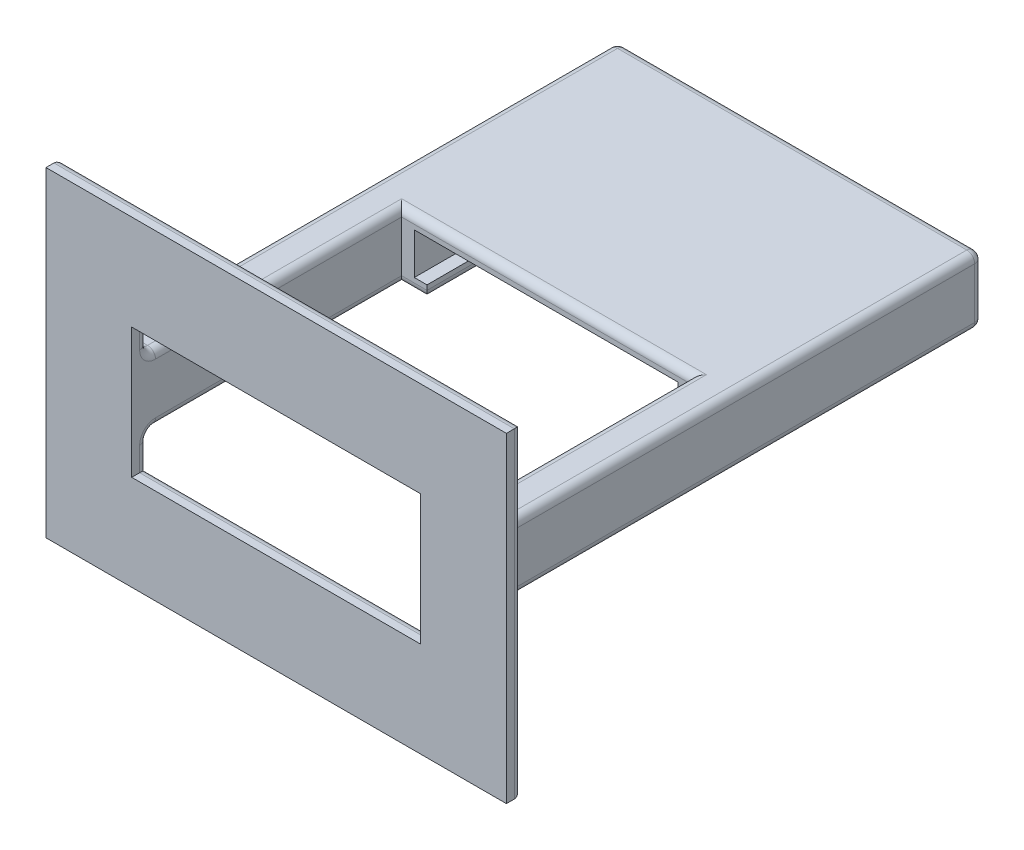
SolidWorks part; units mm, degrees
ref_plane "Front Plane" through (0, 0, 0) normal (0, 0, 1) x (1, 0, 0)
ref_plane "Top Plane" through (0, 0, 0) normal (0, 1, 0) x (1, 0, 0)
ref_plane "Right Plane" through (0, 0, 0) normal (1, 0, 0) x (0, 0, -1)
sketch "Sketch1" plane through (0, 0, 0) normal (0, 1, 0) x (1, 0, 0)
  line L0 (-1.6, -1.6) -> (-1.6, 74)
  line L1 (0, 0) -> (33.2, 0)
  line L2 (0, 0) -> (0, 72.4)
  line L3 (0, 72.4) -> (33.2, 72.4)
  line L4 (33.2, 0) -> (33.2, 72.4)
  line L5 (-1.6, 74) -> (34.8, 74)
  line L6 (34.8, -1.6) -> (34.8, 74)
  line L7 (-1.6, -1.6) -> (34.8, -1.6)
  dimension "D1" = 33.2
  dimension "D2" = 72.4
  dimension "D3" = 1.6
extrude "Boss-Extrude1" add sketch "Sketch1" along normal blind 5.2
sketch "Sketch2" plane through (0, 0, 0) normal (0, 1, 0) x (1, 0, 0)
  line L1 (-1.6, -1.6) -> (34.8, -1.6)
  line L2 (-1.6, -1.6) -> (-1.6, 74)
  line L3 (-1.6, 74) -> (34.8, 74)
  line L4 (34.8, -1.6) -> (34.8, 74)
extrude "Boss-Extrude2" add sketch "Sketch2" against normal blind 1.6
extrude "Boss-Extrude3" add sketch "Sketch2<2>" along normal blind 1.6 from offset 5.2
sketch "Sketch2<2>" plane through (0, 0, 0) normal (0, 1, 0) x (1, 0, 0) same geometry as "Sketch2"
sketch "Sketch3" plane through (0, 6.8, 0) normal (0, 1, 0) x (1, 0, 0)
  line L0 (0, 0) -> (33.2, 0)
  line L1 (0, -1.6) -> (33.2, -1.6)
  line L2 (-1.6, -1.6) -> (34.8, -1.6) construction
  line L3 (0, -1.6) -> (0, 0)
  line L4 (33.2, -1.6) -> (33.2, 0)
  dimension "D1" = 1.6
  dimension "D2" = 1.6
extrude "Cut-Extrude1" cut sketch "Sketch3" against normal blind 5.2 from offset 1.6 offset against normal yes
sketch "Sketch5" plane through (0, -1.6, 0) normal (0, -1, 0) x (1, 0, 0)
  line L0 (1.6, 1.6) -> (31.6, 1.6)
  line L1 (-1.6, 1.6) -> (34.8, 1.6) construction
  line L2 (31.6, 1.6) -> (31.6, -6.4)
  line L4 (1.6, -6.4) -> (1.6, 1.6)
  line L5 (-1.6, -74) -> (-1.6, 1.6) construction
  line L6 (34.8, 1.6) -> (34.8, -74) construction
  arc A0 (1.6, -6.4) -> (31.6, -6.4) centre (16.6, -6.4) ccw
  point P7 (0, 1.6)
  dimension "D1" = 3.2
  dimension "D2" = 3.2
  dimension "D3" = 8
extrude "Cut-Extrude2" cut sketch "Sketch5" against normal blind 2
sketch "Sketch6" plane through (0, 0, 0) normal (0, 1, 0) x (1, 0, 0)
  line L0 (-1.6, 30.4) -> (-1.6, -33.6)
  line L1 (-1.6, 74) -> (-1.6, -1.6) construction
  line L2 (-1.6, -33.6) -> (-6.4, -33.6)
  line L3 (-6.4, -33.6) -> (-6.4, 30.4)
  line L4 (-6.4, 30.4) -> (-1.6, 30.4)
  line L5 (-1.6, -1.6) -> (1.6, -1.6) construction
  line L6 (39.6, 30.4) -> (39.6, -33.6)
  line L7 (39.6, -33.6) -> (34.8, -33.6)
  line L8 (34.8, -33.6) -> (34.8, 30.4)
  line L9 (34.8, 30.4) -> (39.6, 30.4)
  line L10 (34.8, -1.6) -> (34.8, 74) construction
  point P4 (0, 0)
  point P14 (34.8, 30.4)
  dimension "D1" = 32
  dimension "D2" = 4.8
  dimension "D3" = 32
  dimension "D4" = 4.8
extrude "Boss-Extrude5" add sketch "Sketch6" along normal blind 6.8 and the other way blind 1.6
sketch "Sketch7" plane through (0, -1.6, 0) normal (0, -1, 0) x (1, 0, 0)
  line L1 (34.8, -74) -> (-1.6, -74)
  line L2 (34.8, -74) -> (34.8, -30.4)
  line L3 (34.8, -30.4) -> (-1.6, -30.4)
  line L4 (-1.6, -74) -> (-1.6, -30.4)
  point P5 (-1.3371, -30.5564)
  point P6 (-1.6, -30.4)
extrude "Cut-Extrude3" cut sketch "Sketch7" against normal blind 12
sketch "Sketch8" plane through (0, 0, 33.6) normal (0, 0, 1) x (1, 0, 0)
  line L0 (39.6, -1.6) -> (39.6, 6.8) construction
  line L1 (-12.4, 22.8) -> (45.6, 22.8)
  line L2 (-12.4, 22.8) -> (-12.4, -17.6)
  line L3 (-12.4, -17.6) -> (45.6, -17.6)
  line L4 (45.6, 22.8) -> (45.6, -17.6)
  line L5 (-6.4, -1.6) -> (-6.4, 6.8) construction
  line L6 (-6.4, -1.6) -> (-1.6, -1.6) construction
  line L7 (-6.4, 6.8) -> (-1.6, 6.8) construction
  line L9 (-1.6, 10.8) -> (34.8, 10.8)
  line L10 (-1.6, 10.8) -> (-1.6, -5.6)
  line L11 (-1.6, -5.6) -> (34.8, -5.6)
  line L12 (34.8, 10.8) -> (34.8, -5.6)
  line L13 (-1.6, 6.8) -> (-1.6, -1.6) construction
  line L15 (34.8, -1.6) -> (34.8, 6.8) construction
  line L16 (1.6, -1.6) -> (31.6, -1.6) construction
  line L17 (-1.6, 6.8) -> (34.8, 6.8) construction
  dimension "D1" = 6
  dimension "D2" = 6
  dimension "D3" = 16
  dimension "D4" = 16
  dimension "D5" = 4
  dimension "D6" = 4
extrude "Boss-Extrude6" add sketch "Sketch8" along normal blind 2
fillet "Fillet2" radius 1 34 edges at (16.6, -17.6, 33.6) (45.6, 2.6, 33.6) (16.6, 22.8, 33.6) (-12.4, 2.6, 33.6) (-1.6, 8.8, 33.6) (16.6, 10.8, 33.6) (34.8, 8.8, 33.6) (34.8, -3.6, 33.6) (16.6, -5.6, 33.6) (-1.6, -3.6, 33.6) (37.2, 6.8, 33.6) (34.8, 6.8, 17.6) (16.6, 6.8, 1.6) (-1.6, 6.8, 17.6) (-4, 6.8, 33.6) (16.6, 6.8, -30.4) (39.6, 2.6, 33.6) (39.6, 6.8, 1.6) (39.6, 2.6, -30.4) (-4, -1.6, 33.6) (-1.6, -1.6, 17.6) (0, -1.6, 1.6) (1.6, -1.6, -2.4) (16.6, -1.6, -21.4) (31.6, -1.6, -2.4) (33.2, -1.6, 1.6) (34.8, -1.6, 17.6) (37.2, -1.6, 33.6) (39.6, -1.6, 1.6) (16.6, -1.6, -30.4) (-6.4, -1.6, 1.6) (-6.4, 2.6, -30.4) (-6.4, 6.8, 1.6) (-6.4, 2.6, 33.6)
equation "\"D2@Sketch3\"=\"D1@Sketch3\""
equation "\"D2@Sketch5\"=\"D1@Sketch5\""
